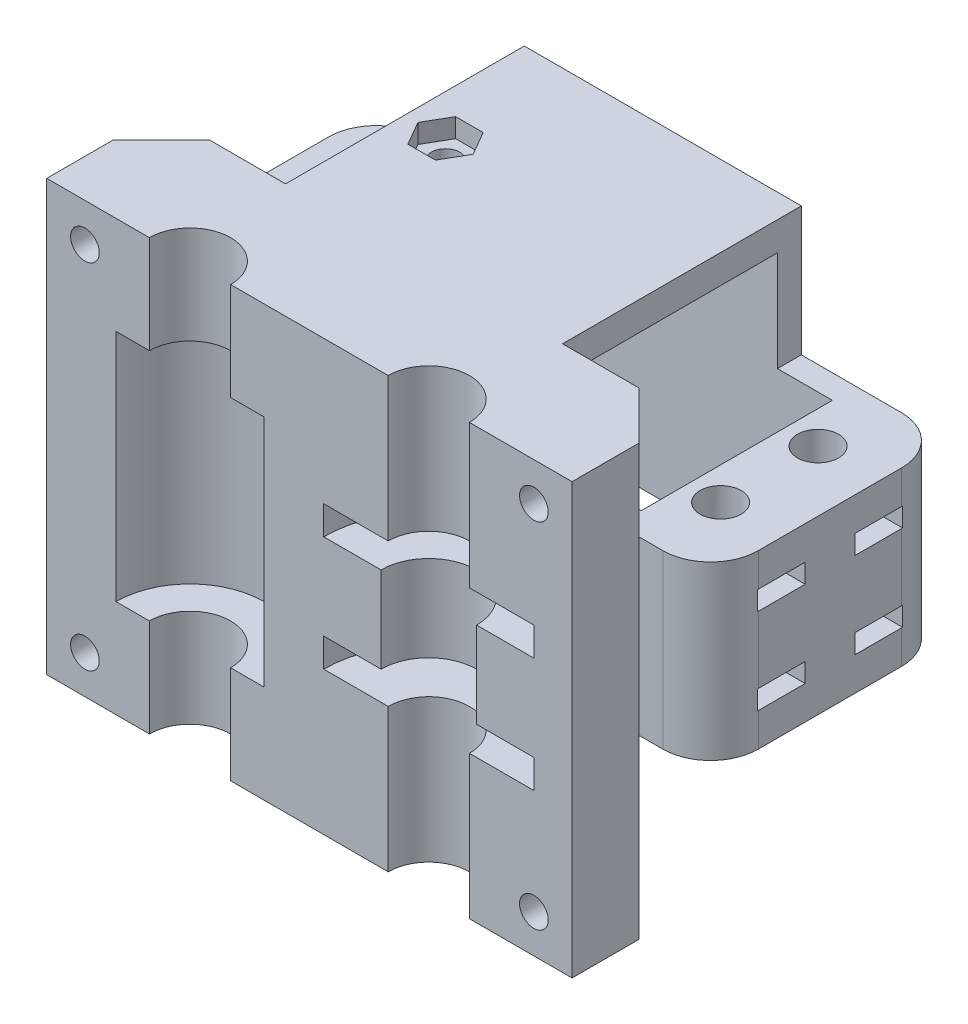
SolidWorks part; units mm, degrees
ref_plane "Plan de face" through (0, 0, 0) normal (0, 0, 1) x (1, 0, 0)
ref_plane "Plan de dessus" through (0, 0, 0) normal (0, 1, 0) x (1, 0, 0)
ref_plane "Plan de droite" through (0, 0, 0) normal (1, 0, 0) x (0, 0, -1)
sketch "Esquisse1" plane through (0, 0, 0) normal (0, 0, 1) x (1, 0, 0)
  line L1 (-27.5, -22.5) -> (27.5, -22.5)
  line L2 (-27.5, -22.5) -> (-27.5, 22.5)
  line L3 (-27.5, 22.5) -> (27.5, 22.5)
  line L4 (27.5, -22.5) -> (27.5, 22.5)
  line L5 (-27.5, -22.5) -> (27.5, 22.5) construction
  line L6 (-27.5, 22.5) -> (27.5, -22.5) construction
  point P0 (0, 0)
  dimension "D1" = 55
  dimension "D2" = 45
extrude "Boss.-Extru.1" add sketch "Esquisse1" along normal blind 12
sketch "Esquisse2" plane through (0, 22.5, 0) normal (0, 1, 0) x (1, 0, 0)
  line L0 (27.5, -12) -> (-27.5, -12) construction
  line L1 (-27.5, -12) -> (-27.5, 0) construction
  line L2 (27.5, -12) -> (27.5, 0) construction
  circle A0 centre (-12.5, -12) radius 4.25
  circle A1 centre (12.5, -12) radius 4.25
  dimension "D1" = 8.5
  dimension "D3" = 8.5
  dimension "D2" = 15
  dimension "D4" = 15
extrude "Enlèv. mat.-Extru.1" cut sketch "Esquisse2" against normal through all
ref_plane "Plan2" through (0, 7.5, 0) normal (0, 1, 0) x (1, 0, 0)
sketch "Esquisse3" plane through (0, 0, 0) normal (0, 1, 0) x (1, 0, 0)
  circle A0 centre (-12.5, -12) radius 7.75
  dimension "D1" = 15.5
extrude "Enlèv. mat.-Extru.2" cut sketch "Esquisse3" against normal blind 12.25 and the other way blind 12.25
sketch "Esquisse4" plane through (0, 7.5, 0) normal (0, 1, 0) x (1, 0, 0)
  circle A0 centre (12.5, -12) radius 11
  dimension "D1" = 22
extrude "Enlèv. mat.-Extru.3" cut sketch "Esquisse4" against normal blind 3
sketch "Esquisse5" plane through (0, 7.5, 0) normal (0, 1, 0) x (1, 0, 0)
  circle A0 centre (12.5, -12) radius 5
  dimension "D1" = 10
extrude "Enlèv. mat.-Extru.4" cut sketch "Esquisse5" against normal blind 15
chamfer "Chanfrein1" [suppressed] distance 10 angle 45
sketch "Esquisse6" plane through (0, 0, 0) normal (0, 0, -1) x (-1, 0, 0)
  line L0 (0, -22.5) -> (0, 22.5) construction
  line L1 (27.5, -22.5) -> (-27.5, -22.5) construction
  line L2 (-27.5, 22.5) -> (27.5, 22.5) construction
  line L3 (27.5, 22.5) -> (27.5, -22.5) construction
  line L4 (27.5, 0) -> (-27.5, 0) construction
  line L5 (-27.5, -22.5) -> (-27.5, 22.5) construction
  circle A0 centre (23.5, -18.5) radius 1.5
  circle A1 centre (-23.5, -18.5) radius 1.5
  circle A2 centre (-23.5, 18.5) radius 1.5
  circle A3 centre (23.5, 18.5) radius 1.5
  dimension "D1" = 3
  dimension "D2" = 4
  dimension "D3" = 4
extrude "Enlèv. mat.-Extru.5" cut sketch "Esquisse6" against normal through all both and the other way through all
sketch "Esquisse7" plane through (0, 0, 0) normal (0, 0, -1) x (-1, 0, 0)
  line L0 (0, -22.5) -> (0, 22.5) construction
  line L1 (27.5, -22.5) -> (-27.5, -22.5) construction
  line L2 (-27.5, 22.5) -> (27.5, 22.5) construction
  line L3 (27.5, 0) -> (-27.5, 0) construction
  line L4 (27.5, 22.5) -> (27.5, -22.5) construction
  line L5 (-27.5, -22.5) -> (-27.5, 22.5) construction
  circle A0 centre (23.5, -18.5) radius 2.5
  circle A1 centre (23.5, 18.5) radius 2.5
  circle A2 centre (-23.5, 18.5) radius 2.5
  circle A3 centre (-23.5, -18.5) radius 2.5
  dimension "D1" = 5
extrude "Enlèv. mat.-Extru.6" cut sketch "Esquisse7" against normal blind 4
chamfer "Chanfrein3" distance 5 angle 45 2 edges at (27.5, 0, 0) (-27.5, 0, 0)
mirror "Symétrie2" about plane through (0, 0, 0) normal (0, 1, 0) of "Enlèv. mat.-Extru.3"
sketch "Esquisse8" plane through (0, 0, 0) normal (0, 0, -1) x (-1, 0, 0)
  line L0 (22.5, -22.5) -> (-22.5, -22.5) construction
  line L1 (-8.5398, -45.608) -> (8.5398, -45.608)
  line L2 (-8.5398, -45.608) -> (-8.5398, 0.608)
  line L3 (-8.5398, 0.608) -> (8.5398, 0.608)
  line L4 (8.5398, -45.608) -> (8.5398, 0.608)
  line L5 (-8.5398, -45.608) -> (8.5398, 0.608) construction
  line L6 (-8.5398, 0.608) -> (8.5398, -45.608) construction
  point P0 (0, -22.5)
sketch "Esquisse9" plane through (0, 0, 0) normal (0, 0, -1) x (-1, 0, 0)
  line L1 (-30, -9) -> (30, -9)
  line L2 (-30, -9) -> (-30, 9)
  line L3 (-30, 9) -> (30, 9)
  line L4 (30, -9) -> (30, 9)
  line L5 (-30, -9) -> (30, 9) construction
  line L6 (-30, 9) -> (30, -9) construction
  point P0 (0, 0)
  dimension "D1" = 18
  dimension "D2" = 60
extrude "Boss.-Extru.2" add sketch "Esquisse9" along normal blind 25
sketch "Esquisse10" plane through (0, 9, 0) normal (0, 1, 0) x (1, 0, 0)
  line L0 (30, 0) -> (-30, 25) construction
  line L2 (-20.25, 22.5) -> (20.25, 22.5)
  line L3 (-20.25, 22.5) -> (-20.25, 2.5)
  line L4 (-20.25, 2.5) -> (20.25, 2.5)
  line L5 (20.25, 22.5) -> (20.25, 2.5)
  line L6 (-20.25, 22.5) -> (20.25, 2.5) construction
  line L7 (-20.25, 2.5) -> (20.25, 22.5) construction
  point P4 (0, 12.5)
  dimension "D1" = 20
  dimension "D2" = 40.5
extrude "Enlèv. mat.-Extru.7" cut sketch "Esquisse10" against normal blind 30
sketch "Esquisse11" plane through (0, -9, 0) normal (0, -1, 0) x (-1, 0, 0)
  circle A0 centre (-23.65, 7.4) radius 2.15
  circle A1 centre (-23.65, 17.6) radius 2.15
  circle A2 centre (24.15, 7.4) radius 2.15
  circle A3 centre (24.15, 17.6) radius 2.15
  dimension "D1" = 4.3
  dimension "D2" = 4.3
extrude "Enlèv. mat.-Extru.8" cut sketch "Esquisse11" against normal through all
fillet "Congé2" radius 5 2 edges at (-30, 0, 0) (30, 0, 0)
fillet "Congé3" radius 5 2 edges at (30, 0, -25) (-30, 0, -25)
sketch "Esquisse12" plane through (30, 0, 0) normal (1, 0, 0) x (0, 0, -1)
  line L0 (5.25, 9) -> (9.55, 9) construction
  line L1 (7.4, 9) -> (7.4, -9) construction
  line L2 (0, -9) -> (5, -9) construction
  line L3 (5, 9) -> (0, 9) construction
  line L4 (9.55, -9) -> (9.55, 9) construction
  line L5 (12.5, 9) -> (12.5, -9) construction
  line L6 (4.9, 3.5) -> (9.9, 3.5)
  line L7 (4.9, 3.5) -> (4.9, 5.5)
  line L8 (4.9, 5.5) -> (9.9, 5.5)
  line L9 (9.9, 3.5) -> (9.9, 5.5)
  line L10 (4.9, 3.5) -> (9.9, 5.5) construction
  line L11 (4.9, 5.5) -> (9.9, 3.5) construction
  line L12 (20, 9) -> (5, 9) construction
  line L13 (20, -9) -> (5, -9) construction
  line L14 (20.1, 3.5) -> (20.1, 5.5)
  line L15 (20.1, 3.5) -> (15.1, 3.5)
  line L16 (20.1, 5.5) -> (15.1, 5.5)
  line L17 (15.1, 3.5) -> (15.1, 5.5)
  point P17 (7.4, 4.5)
  dimension "D1" = 5
  dimension "D2" = 2
  dimension "D3" = 7
extrude "Enlèv. mat.-Extru.9" cut sketch "Esquisse12" against normal blind 9
mirror "Symétrie3" about plane through (0, 0, 0) normal (1, 0, 0) of "Enlèv. mat.-Extru.9"
mirror "Symétrie4" about plane through (0, 0, 0) normal (0, 1, 0) of "Symétrie3", "Enlèv. mat.-Extru.9"
sketch "Esquisse13" plane through (0, 0, 0) normal (0, 0, -1) x (-1, 0, 0)
  line L0 (-14.5, 22.5) -> (14.5, 22.5)
  line L1 (-14.5, 22.5) -> (-14.5, 19.5)
  line L2 (14.5, 22.5) -> (14.5, 19.5)
  line L3 (-14.5, 19.5) -> (14.5, 19.5)
  line L4 (22.5, 9) -> (22.5, 16.2087) construction
  line L5 (-22.5, 22.5) -> (22.5, 22.5) construction
  line L6 (-22.5, 22.5) -> (-22.5, 20.7913) construction
  dimension "D1" = 3
  dimension "D2" = 8
  dimension "D3" = 8
extrude "Boss.-Extru.3" add sketch "Esquisse13" along normal up to surface (25 mm away) up to face at (0, 0, -25)
sketch "Esquisse14" plane through (0, 9, 0) normal (0, 1, 0) x (1, 0, 0)
  line L0 (-14.5, 25) -> (14.5, 25)
  line L1 (-14.5, 25) -> (-14.5, 22.5)
  line L2 (14.5, 25) -> (14.5, 22.5)
  line L3 (-14.5, 22.5) -> (14.5, 22.5)
  line L4 (-25, 25) -> (25, 25) construction
  line L5 (20.25, 22.5) -> (-20.25, 22.5) construction
  line L6 (14.5, 25) -> (14.5, 0) construction
  line L7 (-14.5, 25) -> (-14.5, 0) construction
extrude "Boss.-Extru.4" add sketch "Esquisse14" along normal up to next
sketch "Esquisse15" plane through (0, 22.5, 0) normal (0, 1, 0) x (1, 0, 0)
  circle A0 centre (-10.25, 12.5) radius 1.5
  dimension "D1" = 3
extrude "Enlèv. mat.-Extru.10" cut sketch "Esquisse15" against normal blind 9
sketch "Esquisse16" plane through (0, 22.5, 0) normal (0, 1, 0) x (1, 0, 0)
  line L0 (14.5, 25) -> (-14.5, 25) construction
  line L1 (-8.8066, 15) -> (-11.6934, 15)
  line L2 (-11.6934, 15) -> (-13.1368, 12.5)
  line L3 (-13.1368, 12.5) -> (-11.6934, 10)
  line L4 (-11.6934, 10) -> (-8.8066, 10)
  line L5 (-8.8066, 10) -> (-7.3632, 12.5)
  line L6 (-7.3632, 12.5) -> (-8.8066, 15)
  circle A0 centre (-10.25, 12.5) radius 2.5 construction
  dimension "D1" = 5
extrude "Enlèv. mat.-Extru.11" cut sketch "Esquisse16" against normal blind 2
